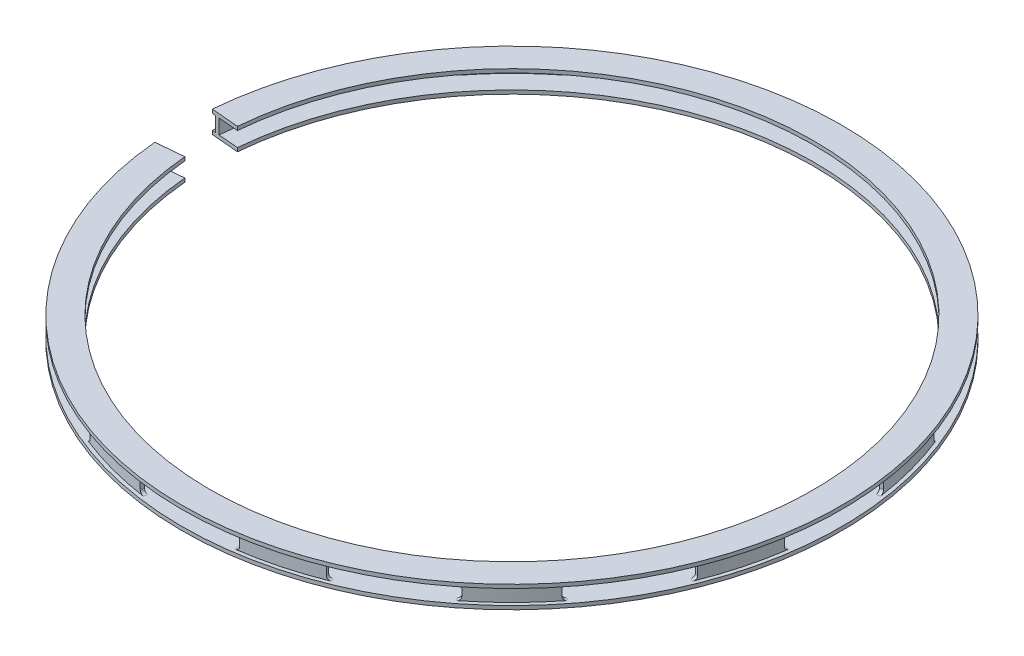
SolidWorks part; units mm, degrees
material "Teak"
ref_plane "Plano frontal" through (0, 0, 0) normal (0, 0, 1) x (1, 0, 0)
ref_plane "Plano superior" through (0, 0, 0) normal (0, 1, 0) x (1, 0, 0)
ref_plane "Plano direito" through (0, 0, 0) normal (1, 0, 0) x (0, 0, -1)
sketch "Sketch1" plane through (0, 0, 0) normal (0, 0, 1) x (1, 0, 0)
  line L0 (0, 0) -> (0, 7.05) construction
  line L1 (41, 0) -> (44.75, 0)
  line L2 (44.75, 0) -> (44.75, 0.5)
  line L3 (44.75, 0.5) -> (44.25, 0.5)
  line L4 (44.25, 0.5) -> (44.25, 2.5)
  line L5 (44.25, 2.5) -> (44.75, 2.5)
  line L6 (44.75, 2.5) -> (44.75, 3)
  line L7 (44.75, 3) -> (41, 3)
  line L8 (41, 3) -> (41, 2.5)
  line L9 (41, 2.5) -> (43.75, 2.5)
  line L10 (43.75, 2.5) -> (43.75, 0.5)
  line L11 (43.75, 0.5) -> (41, 0.5)
  line L12 (41, 0.5) -> (41, 0)
  dimension "D1" = 3.75
  dimension "D2" = 0.5
  dimension "D3" = 1
  dimension "D4" = 3
  dimension "D5" = 2
  dimension "D6" = 0.5
  dimension "D7" = 41
revolve "Revolve1" add sketch "Sketch1" angle 350 mid plane about L0
sketch "Sketch2" plane through (0, 0, 0) normal (0, 0, 1) x (1, 0, 0)
  line L0 (0, 0) -> (0, 17.702) construction
  line L6 (-44.0816, 2.5) -> (44.25, 2.5) construction
  line L7 (44.25, 0.5) -> (43.25, 0.5)
  line L8 (44.25, 0.5) -> (44.25, 2.5)
  line L9 (44.25, 2.5) -> (43.25, 2.5)
  line L10 (43.25, 0.5) -> (43.25, 2.5)
  dimension "D1" = 1
revolve "Cut-Revolve3" cut sketch "Sketch2" angle 17.5 mid plane about L0
fillet "Fillet1" radius 0.5 4 edges at (43.4879, 2.5, 6.6934) (43.4879, 0.5, 6.6934) (43.4879, 0.5, -6.6934) (43.4879, 2.5, -6.6934)
pattern_circular "CirPattern4" count 12 over 360 about axis through (0, 3, 0) along (0, -1, 0) skipping 6 of "Fillet1", "Cut-Revolve3"
